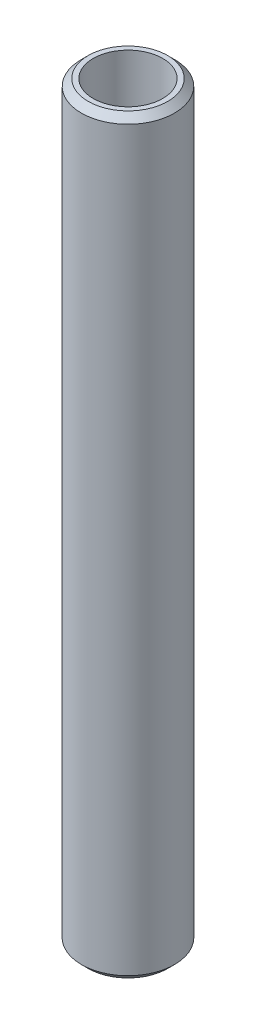
SolidWorks part; units mm, degrees
ref_plane "Front Plane" through (0, 0, 0) normal (0, 0, 1) x (1, 0, 0)
ref_plane "Top Plane" through (0, 0, 0) normal (0, 1, 0) x (1, 0, 0)
ref_plane "Right Plane" through (0, 0, 0) normal (1, 0, 0) x (0, 0, -1)
sketch "Sketch1" plane through (0, 0, 0) normal (0, 1, 0) x (1, 0, 0)
  circle A0 centre (0, 0) radius 35
  dimension "SHAFT_OD" = 70
extrude "Boss-Extrude1" add sketch "Sketch1" along normal blind 564.7275
sketch "Sketch2" plane through (0, 0, 0) normal (0, 1, 0) x (1, 0, 0)
  circle A0 centre (0, 0) radius 26.1412
  dimension "BORE_D" = 52.2825
extrude "Cut-Extrude1" cut sketch "Sketch2" along normal through all
chamfer "Chamfer1" distance 5.0912 angle 45 2 edges at (0, 564.7275, 35) (0, 0, 35)
